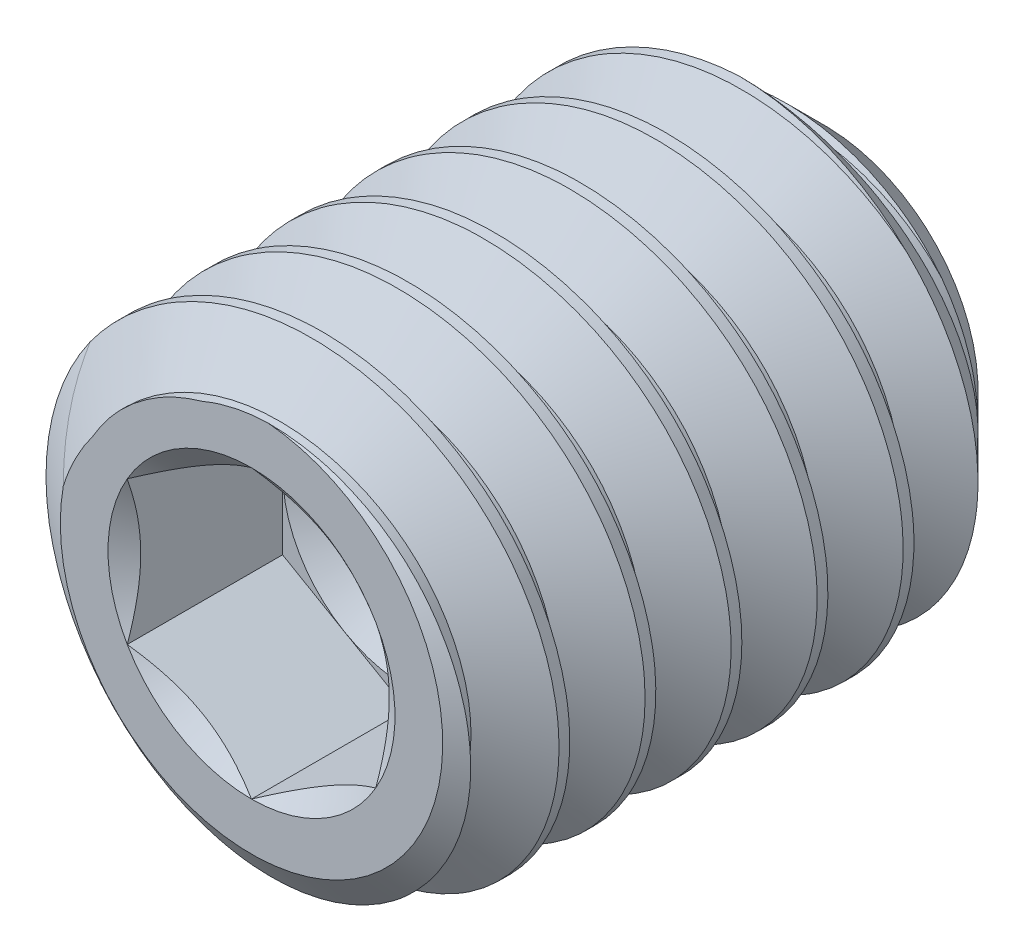
SolidWorks part; units mm, degrees
ref_plane "Front" through (0, 0, 0) normal (0, 0, 1) x (1, 0, 0)
ref_plane "Top" through (0, 0, 0) normal (0, 1, 0) x (1, 0, 0)
ref_plane "Right" through (0, 0, 0) normal (1, 0, 0) x (0, 0, -1)
sketch "Sketch22" plane through (0, 0, 0) normal (1, 0, 0) x (0, 0, -1)
  line L0 (-1.5, 0) -> (-1.5, 1)
  line L1 (-1.5, 1) -> (-1.3249, 1.25)
  line L2 (-1.3249, 1.25) -> (1.05, 1.25)
  line L3 (1.05, 1.25) -> (1.5, 0.8)
  line L4 (-0.1375, 1.25) -> (-0.1375, -1.25) construction
  line L5 (1.5, 0) -> (-1.5, 0)
  line L6 (-1.5, 1) -> (-1.5, -1) construction
  line L7 (1.5, 0) -> (1.5, 0.8)
  point P11 (-0.1375, 0)
  dimension "Length" = 3
  dimension "D3" = 35
  dimension "D6" = 45
  dimension "Dia" = 2.5
  dimension "D1" = 2
  dimension "D2" = 0.45
revolve "Revolve1" add sketch "Sketch22" angle 360 about L5
ref_plane "Plane1" through (0, 0, -1.5) normal (0, 0, 1) x (1, 0, 0)
sketch "Sketch23" plane through (0, 0, 1.5) normal (0, 0, 1) x (1, 0, 0)
  line L1 (0, 0.7506) -> (-0.65, 0.3753)
  line L2 (-0.65, 0.3753) -> (-0.65, -0.3753)
  line L3 (-0.65, -0.3753) -> (0, -0.7506)
  line L4 (0, -0.7506) -> (0.65, -0.3753)
  line L5 (0.65, -0.3753) -> (0.65, 0.3753)
  line L6 (0.65, 0.3753) -> (0, 0.7506)
  circle A0 centre (0, 0) radius 0.65 construction
  dimension "Hex" = 1.3
extrude "Cut-Extrude10" cut sketch "Sketch23" against normal blind 0.8125
sketch "Sketch24" plane through (0, 0, 1.5) normal (0, 0, 1) x (1, 0, 0)
  circle A0 centre (0, 0) radius 0.7506
extrude "Cut-Extrude11" cut sketch "Sketch24" against normal through all draft 55
sketch "Sketch26" plane through (0, 0, 0.6875) normal (0, 0, 1) x (1, 0, 0)
  circle A0 centre (0, 0) radius 0.65 construction
  circle A1 centre (0, 0) radius 0.65
extrude "Cut-Extrude12" cut sketch "Sketch26" against normal through all draft 60
sketch "Sketch30" plane through (0, 0, 0) normal (1, 0, 0) x (0, 0, -1)
  line L0 (-1.3249, 1.25) -> (1.05, 1.25) construction
  line L1 (-1.5, 0) -> (-1.5, 1) construction
  line L2 (1.5, 0) -> (1.5, 0.8) construction
  point P0 (-1.5, 1.25)
  point P1 (1.5, 1.25)
  point P2 (1.5, -1.25)
  point P11 (0.375, -1.25)
  dimension "D1" = 1.125
sketch "Sketch27" plane through (0, 0, -1.5) normal (0, 0, 1) x (1, 0, 0)
  circle A0 centre (0, 0) radius 1.25 construction
  circle A1 centre (0, 0) radius 1.25
curve "Helix/Spiral1" pitch 0.45 height 3.45 radius 1.25 centre (0, 0, -1.5) axis (0, 0, 1) start towards (0, 1, 0)
sketch "Sketch28" plane through (0, 0, 0) normal (1, 0, 0) x (0, 0, -1)
  line L0 (1.5, 1.25) -> (1.8937, 1.25)
  line L1 (1.8937, 1.25) -> (1.725, 0.9577)
  line L2 (1.725, 0.9577) -> (1.6687, 0.9577)
  line L3 (1.6687, 0.9577) -> (1.5, 1.25)
  line L4 (1.5844, 1.1039) -> (1.8094, 1.1039) construction
  line L6 (-1.3249, 1.25) -> (1.05, 1.25) construction
  dimension "D1" = 0.0563
  dimension "D3" = 60
  dimension "D2" = 0.225
sweep "Cut-Sweep2" cut profiles "Sketch28" path "Helix/Spiral1"
ref_plane "Contact Plane 1" through (0, 0, 1.5) normal (0, 0, 1) x (1, 0, 0)
ref_plane "Contact Plane 2" through (0, 0, -1.5) normal (0, 0, -1) x (-1, 0, 0)
ref_axis "Center Axis 1" through (0, 0, -1.5) along (0, 0, 1)
equation "\"D1@Sketch28\" = \"D4@Helix/Spiral1\" * .125"
equation "\"D2@Sketch28\" = \"D4@Helix/Spiral1\" * .5"
equation "\"D3@Helix/Spiral1\" = \"Length@Sketch22\" + \"D4@Helix/Spiral1\""
equation "\"D1@Sketch30\" = \"D4@Helix/Spiral1\" * 2.5"
equation "\"hex Depth@Cut-Extrude10\" = \"Hex@Sketch23\" * .625"
equation "\"D1@Sketch22\" = \"Dia@Sketch22\" * .8"
equation "\"D2@Sketch22\" = \"D4@Helix/Spiral1\""
